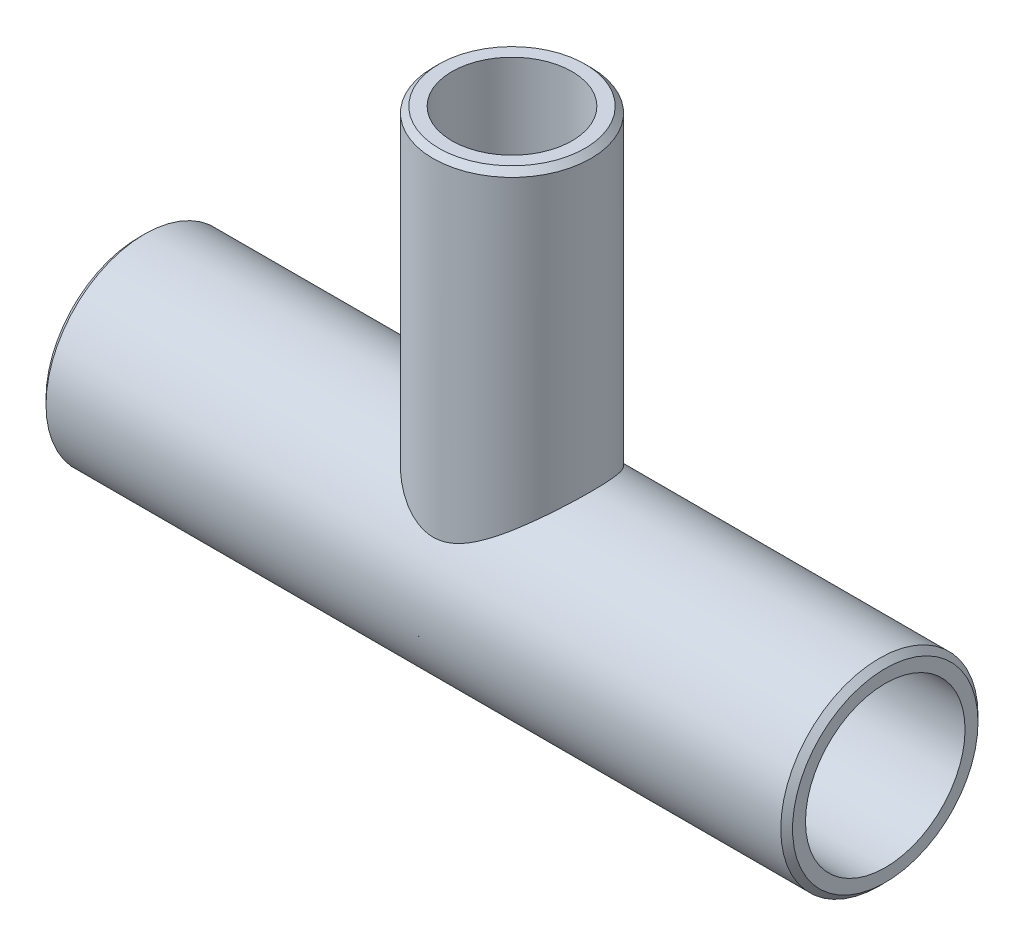
SolidWorks part; units mm, degrees
ref_plane "Спереди" through (0, 0, 0) normal (0, 0, 1) x (1, 0, 0)
ref_plane "Сверху" through (0, 0, 0) normal (0, 1, 0) x (1, 0, 0)
ref_plane "Справа" through (0, 0, 0) normal (1, 0, 0) x (0, 0, -1)
sketch "RunRoute" plane through (0, 0, 0) normal (1, 0, 0) x (0, 0, -1)
  circle A0 centre (0, 0) radius 16.75
  dimension "Diameter" = 33.5
extrude "RunExtrude" add sketch "RunRoute" along normal blind 63.4
mirror "RunExtrudeMirror" about plane through (0, 0, 0) normal (1, 0, 0) of "RunExtrude"
sketch "OutletRoute" plane through (0, 0, 0) normal (0, 1, 0) x (1, 0, 0)
  circle A0 centre (0, 0) radius 13.4
  dimension "Diameter" = 26.8
extrude "OutletExtrude" add sketch "OutletRoute" along normal blind 66.75
shell "TeeShell" thickness 3.2 removed face at (-63.4, 0, -16.75) removed face at (63.4, 0, -16.75) removed face at (0, 66.75, 13.4)
chamfer "TeeChamfer" distance 1 angle 45 3 edges at (0, 66.75, 13.4) (63.4, 0, -16.75) (-63.4, 0, -16.75)
sketch "Sketch1" plane through (0, 0, 0) normal (0, 0, 1) x (1, 0, 0)
  line L0 (12.4, 66.75) -> (-12.4, 66.75) construction
  line L1 (63.4, -15.75) -> (63.4, 15.75) construction
  line L2 (-63.4, 15.75) -> (-63.4, -15.75) construction
  point P0 (0, 66.75)
  point P1 (63.4, 0)
  point P4 (-63.4, 0)
  point P7 (0, 0)
other "CPoint1" parameters "Diameter"=25, "StubLength"=0
ref_axis "Axis2" through (-73.4, 0, 0) along (1, 0, 0)
other "CPoint2" parameters "Diameter"=20, "StubLength"=0
ref_axis "Axis3" through (0, 76.75, 0) along (0, -1, 0)
other "CPoint3" parameters "Diameter"=25, "StubLength"=0
ref_axis "Axis4" through (73.4, 0, 0) along (-1, 0, 0)
other "RPoint1"
